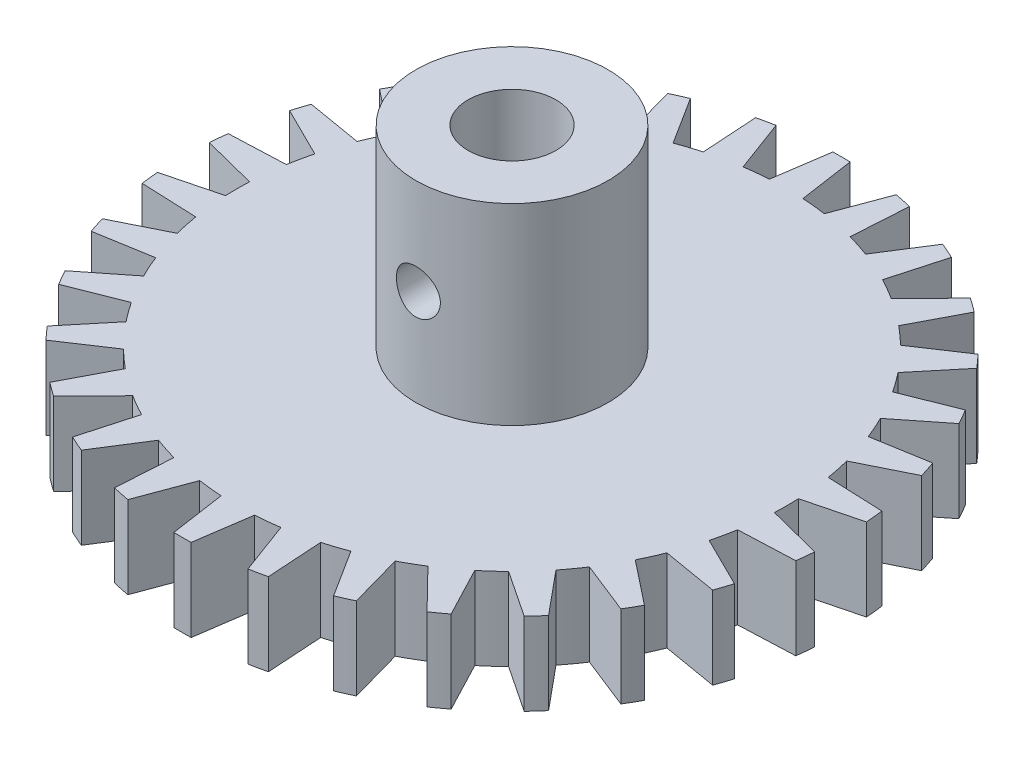
SolidWorks part; units mm, degrees
ref_plane "Front Plane" through (0, 0, 0) normal (0, 0, 1) x (1, 0, 0)
ref_plane "Top Plane" through (0, 0, 0) normal (0, 1, 0) x (1, 0, 0)
ref_plane "Right Plane" through (0, 0, 0) normal (1, 0, 0) x (0, 0, -1)
sketch "Sketch1" plane through (0, 0, 0) normal (0, 1, 0) x (1, 0, 0)
  line L0 (0, 0) -> (0, 12) construction
  line L1 (0, 0) -> (-0.3141, 11.9959) construction
  line L2 (0, 0) -> (-0.6105, 9.9813) construction
  line L3 (0, 0) -> (-1.0453, 9.9452) construction
  line L4 (-0.3141, 11.9959) -> (-0.6105, 9.9813)
  line L5 (0.3141, 11.9959) -> (0.6105, 9.9813)
  line L6 (2.1868, 11.7991) -> (1.4781, 9.8902)
  line L7 (2.8013, 11.6684) -> (2.6724, 9.6363)
  line L8 (4.5922, 11.0866) -> (3.5021, 9.3667)
  line L9 (5.1661, 10.831) -> (4.6175, 8.8701)
  line L10 (6.7969, 9.8895) -> (5.373, 8.4339)
  line L11 (7.3051, 9.5202) -> (6.3608, 7.7162)
  line L12 (8.7045, 8.2603) -> (7.0091, 7.1325)
  line L13 (9.1249, 7.7934) -> (7.8261, 6.2251)
  line L14 (10.2317, 6.27) -> (8.3389, 5.5194)
  line L15 (10.5458, 5.7259) -> (8.9493, 4.462)
  line L16 (11.3117, 4.0057) -> (9.3042, 3.665)
  line L17 (11.5058, 3.4082) -> (9.6815, 2.5038)
  line L18 (11.8973, 1.5663) -> (9.8629, 1.6505)
  line L19 (11.963, 0.9415) -> (9.9905, 0.4362)
  line L20 (11.963, -0.9415) -> (9.9905, -0.4362)
  line L21 (11.8973, -1.5663) -> (9.8629, -1.6505)
  line L22 (11.5058, -3.4082) -> (9.6815, -2.5038)
  line L23 (11.3117, -4.0057) -> (9.3042, -3.665)
  line L24 (10.5458, -5.7259) -> (8.9493, -4.462)
  line L25 (10.2317, -6.27) -> (8.3389, -5.5194)
  line L26 (9.1249, -7.7934) -> (7.8261, -6.2251)
  line L27 (8.7045, -8.2603) -> (7.0091, -7.1325)
  line L28 (7.3051, -9.5202) -> (6.3608, -7.7162)
  line L29 (6.7969, -9.8895) -> (5.373, -8.4339)
  line L30 (5.1661, -10.831) -> (4.6175, -8.8701)
  line L31 (4.5922, -11.0866) -> (3.5021, -9.3667)
  line L32 (2.8013, -11.6684) -> (2.6724, -9.6363)
  line L33 (2.1868, -11.7991) -> (1.4781, -9.8902)
  line L34 (0.3141, -11.9959) -> (0.6105, -9.9813)
  line L35 (-0.3141, -11.9959) -> (-0.6105, -9.9813)
  line L36 (-2.1868, -11.7991) -> (-1.4781, -9.8902)
  line L37 (-2.8013, -11.6684) -> (-2.6724, -9.6363)
  line L38 (-4.5922, -11.0866) -> (-3.5021, -9.3667)
  line L39 (-5.1661, -10.831) -> (-4.6175, -8.8701)
  line L40 (-6.7969, -9.8895) -> (-5.373, -8.4339)
  line L41 (-7.3051, -9.5202) -> (-6.3608, -7.7162)
  line L42 (-8.7045, -8.2603) -> (-7.0091, -7.1325)
  line L43 (-9.1249, -7.7934) -> (-7.8261, -6.2251)
  line L44 (-10.2317, -6.27) -> (-8.3389, -5.5194)
  line L45 (-10.5458, -5.7259) -> (-8.9493, -4.462)
  line L46 (-11.3117, -4.0057) -> (-9.3042, -3.665)
  line L47 (-11.5058, -3.4082) -> (-9.6815, -2.5038)
  line L48 (-11.8973, -1.5663) -> (-9.8629, -1.6505)
  line L49 (-11.963, -0.9415) -> (-9.9905, -0.4362)
  line L50 (-11.963, 0.9415) -> (-9.9905, 0.4362)
  line L51 (-11.8973, 1.5663) -> (-9.8629, 1.6505)
  line L52 (-11.5058, 3.4082) -> (-9.6815, 2.5038)
  line L53 (-11.3117, 4.0057) -> (-9.3042, 3.665)
  line L54 (-10.5458, 5.7259) -> (-8.9493, 4.462)
  line L55 (-10.2317, 6.27) -> (-8.3389, 5.5194)
  line L56 (-9.1249, 7.7934) -> (-7.8261, 6.2251)
  line L57 (-8.7045, 8.2603) -> (-7.0091, 7.1325)
  line L58 (-7.3051, 9.5202) -> (-6.3608, 7.7162)
  line L59 (-6.7969, 9.8895) -> (-5.373, 8.4339)
  line L60 (-5.1661, 10.831) -> (-4.6175, 8.8701)
  line L61 (-4.5922, 11.0866) -> (-3.5021, 9.3667)
  line L62 (-2.8013, 11.6684) -> (-2.6724, 9.6363)
  line L63 (-2.1868, 11.7991) -> (-1.4781, 9.8902)
  arc A0 (0.3141, 11.9959) -> (-0.3141, 11.9959) centre (0, 0) ccw
  arc A1 (-0.6105, 9.9813) -> (-1.0453, 9.9452) centre (0, 0) ccw
  arc A2 (0.6105, 9.9813) -> (1.0453, 9.9452) centre (0, 0) cw
  arc A4 (2.8013, 11.6684) -> (2.1868, 11.7991) centre (0, 0) ccw
  arc A5 (1.4781, 9.8902) -> (1.0453, 9.9452) centre (0, 0) ccw
  arc A6 (2.6724, 9.6363) -> (3.0902, 9.5106) centre (0, 0) cw
  arc A7 (5.1661, 10.831) -> (4.5922, 11.0866) centre (0, 0) ccw
  arc A8 (3.5021, 9.3667) -> (3.0902, 9.5106) centre (0, 0) ccw
  arc A9 (4.6175, 8.8701) -> (5, 8.6603) centre (0, 0) cw
  arc A10 (7.3051, 9.5202) -> (6.7969, 9.8895) centre (0, 0) ccw
  arc A11 (5.373, 8.4339) -> (5, 8.6603) centre (0, 0) ccw
  arc A12 (6.3608, 7.7162) -> (6.6913, 7.4314) centre (0, 0) cw
  arc A13 (9.1249, 7.7934) -> (8.7045, 8.2603) centre (0, 0) ccw
  arc A14 (7.0091, 7.1325) -> (6.6913, 7.4314) centre (0, 0) ccw
  arc A15 (7.8261, 6.2251) -> (8.0902, 5.8779) centre (0, 0) cw
  arc A16 (10.5458, 5.7259) -> (10.2317, 6.27) centre (0, 0) ccw
  arc A17 (8.3389, 5.5194) -> (8.0902, 5.8779) centre (0, 0) ccw
  arc A18 (8.9493, 4.462) -> (9.1355, 4.0674) centre (0, 0) cw
  arc A19 (11.5058, 3.4082) -> (11.3117, 4.0057) centre (0, 0) ccw
  arc A20 (9.3042, 3.665) -> (9.1355, 4.0674) centre (0, 0) ccw
  arc A21 (9.6815, 2.5038) -> (9.7815, 2.0791) centre (0, 0) cw
  arc A22 (11.963, 0.9415) -> (11.8973, 1.5663) centre (0, 0) ccw
  arc A23 (9.8629, 1.6505) -> (9.7815, 2.0791) centre (0, 0) ccw
  arc A24 (9.9905, 0.4362) -> (10, 0) centre (0, 0) cw
  arc A25 (11.8973, -1.5663) -> (11.963, -0.9415) centre (0, 0) ccw
  arc A26 (9.9905, -0.4362) -> (10, 0) centre (0, 0) ccw
  arc A27 (9.8629, -1.6505) -> (9.7815, -2.0791) centre (0, 0) cw
  arc A28 (11.3117, -4.0057) -> (11.5058, -3.4082) centre (0, 0) ccw
  arc A29 (9.6815, -2.5038) -> (9.7815, -2.0791) centre (0, 0) ccw
  arc A30 (9.3042, -3.665) -> (9.1355, -4.0674) centre (0, 0) cw
  arc A31 (10.2317, -6.27) -> (10.5458, -5.7259) centre (0, 0) ccw
  arc A32 (8.9493, -4.462) -> (9.1355, -4.0674) centre (0, 0) ccw
  arc A33 (8.3389, -5.5194) -> (8.0902, -5.8779) centre (0, 0) cw
  arc A34 (8.7045, -8.2603) -> (9.1249, -7.7934) centre (0, 0) ccw
  arc A35 (7.8261, -6.2251) -> (8.0902, -5.8779) centre (0, 0) ccw
  arc A36 (7.0091, -7.1325) -> (6.6913, -7.4314) centre (0, 0) cw
  arc A37 (6.7969, -9.8895) -> (7.3051, -9.5202) centre (0, 0) ccw
  arc A38 (6.3608, -7.7162) -> (6.6913, -7.4314) centre (0, 0) ccw
  arc A39 (5.373, -8.4339) -> (5, -8.6603) centre (0, 0) cw
  arc A40 (4.5922, -11.0866) -> (5.1661, -10.831) centre (0, 0) ccw
  arc A41 (4.6175, -8.8701) -> (5, -8.6603) centre (0, 0) ccw
  arc A42 (3.5021, -9.3667) -> (3.0902, -9.5106) centre (0, 0) cw
  arc A43 (2.1868, -11.7991) -> (2.8013, -11.6684) centre (0, 0) ccw
  arc A44 (2.6724, -9.6363) -> (3.0902, -9.5106) centre (0, 0) ccw
  arc A45 (1.4781, -9.8902) -> (1.0453, -9.9452) centre (0, 0) cw
  arc A46 (-0.3141, -11.9959) -> (0.3141, -11.9959) centre (0, 0) ccw
  arc A47 (0.6105, -9.9813) -> (1.0453, -9.9452) centre (0, 0) ccw
  arc A48 (-0.6105, -9.9813) -> (-1.0453, -9.9452) centre (0, 0) cw
  arc A49 (-2.8013, -11.6684) -> (-2.1868, -11.7991) centre (0, 0) ccw
  arc A50 (-1.4781, -9.8902) -> (-1.0453, -9.9452) centre (0, 0) ccw
  arc A51 (-2.6724, -9.6363) -> (-3.0902, -9.5106) centre (0, 0) cw
  arc A52 (-5.1661, -10.831) -> (-4.5922, -11.0866) centre (0, 0) ccw
  arc A53 (-3.5021, -9.3667) -> (-3.0902, -9.5106) centre (0, 0) ccw
  arc A54 (-4.6175, -8.8701) -> (-5, -8.6603) centre (0, 0) cw
  arc A55 (-7.3051, -9.5202) -> (-6.7969, -9.8895) centre (0, 0) ccw
  arc A56 (-5.373, -8.4339) -> (-5, -8.6603) centre (0, 0) ccw
  arc A57 (-6.3608, -7.7162) -> (-6.6913, -7.4314) centre (0, 0) cw
  arc A58 (-9.1249, -7.7934) -> (-8.7045, -8.2603) centre (0, 0) ccw
  arc A59 (-7.0091, -7.1325) -> (-6.6913, -7.4314) centre (0, 0) ccw
  arc A60 (-7.8261, -6.2251) -> (-8.0902, -5.8779) centre (0, 0) cw
  arc A61 (-10.5458, -5.7259) -> (-10.2317, -6.27) centre (0, 0) ccw
  arc A62 (-8.3389, -5.5194) -> (-8.0902, -5.8779) centre (0, 0) ccw
  arc A63 (-8.9493, -4.462) -> (-9.1355, -4.0674) centre (0, 0) cw
  arc A64 (-11.5058, -3.4082) -> (-11.3117, -4.0057) centre (0, 0) ccw
  arc A65 (-9.3042, -3.665) -> (-9.1355, -4.0674) centre (0, 0) ccw
  arc A66 (-9.6815, -2.5038) -> (-9.7815, -2.0791) centre (0, 0) cw
  arc A67 (-11.963, -0.9415) -> (-11.8973, -1.5663) centre (0, 0) ccw
  arc A68 (-9.8629, -1.6505) -> (-9.7815, -2.0791) centre (0, 0) ccw
  arc A69 (-9.9905, -0.4362) -> (-10, 0) centre (0, 0) cw
  arc A70 (-11.8973, 1.5663) -> (-11.963, 0.9415) centre (0, 0) ccw
  arc A71 (-9.9905, 0.4362) -> (-10, 0) centre (0, 0) ccw
  arc A72 (-9.8629, 1.6505) -> (-9.7815, 2.0791) centre (0, 0) cw
  arc A73 (-11.3117, 4.0057) -> (-11.5058, 3.4082) centre (0, 0) ccw
  arc A74 (-9.6815, 2.5038) -> (-9.7815, 2.0791) centre (0, 0) ccw
  arc A75 (-9.3042, 3.665) -> (-9.1355, 4.0674) centre (0, 0) cw
  arc A76 (-10.2317, 6.27) -> (-10.5458, 5.7259) centre (0, 0) ccw
  arc A77 (-8.9493, 4.462) -> (-9.1355, 4.0674) centre (0, 0) ccw
  arc A78 (-8.3389, 5.5194) -> (-8.0902, 5.8779) centre (0, 0) cw
  arc A79 (-8.7045, 8.2603) -> (-9.1249, 7.7934) centre (0, 0) ccw
  arc A80 (-7.8261, 6.2251) -> (-8.0902, 5.8779) centre (0, 0) ccw
  arc A81 (-7.0091, 7.1325) -> (-6.6913, 7.4314) centre (0, 0) cw
  arc A82 (-6.7969, 9.8895) -> (-7.3051, 9.5202) centre (0, 0) ccw
  arc A83 (-6.3608, 7.7162) -> (-6.6913, 7.4314) centre (0, 0) ccw
  arc A84 (-5.373, 8.4339) -> (-5, 8.6603) centre (0, 0) cw
  arc A85 (-4.5922, 11.0866) -> (-5.1661, 10.831) centre (0, 0) ccw
  arc A86 (-4.6175, 8.8701) -> (-5, 8.6603) centre (0, 0) ccw
  arc A87 (-3.5021, 9.3667) -> (-3.0902, 9.5106) centre (0, 0) cw
  arc A88 (-2.1868, 11.7991) -> (-2.8013, 11.6684) centre (0, 0) ccw
  arc A89 (-2.6724, 9.6363) -> (-3.0902, 9.5106) centre (0, 0) ccw
  arc A90 (-1.4781, 9.8902) -> (-1.0453, 9.9452) centre (0, 0) cw
  point P185 (0, 0)
  dimension "D1" = 1.5
  dimension "D2" = 2
  dimension "D3" = 2.5
  dimension "D4" = 30
  dimension "D5" = 10
extrude "Boss-Extrude1" add sketch "Sketch1" along normal blind 3
sketch "Sketch3" plane through (0, 3, 0) normal (0, 1, 0) x (1, 0, 0)
  circle A1 centre (0, 0) radius 3.5
  dimension "D2" = 7
extrude "Boss-Extrude2" add sketch "Sketch3" along normal blind 7
sketch "Sketch2" plane through (0, 3, 0) normal (0, 1, 0) x (1, 0, 0)
  circle A0 centre (0, 0) radius 1.6
  dimension "D1" = 3.2
extrude "Cut-Extrude1" cut sketch "Sketch2" against normal through all and the other way through all
sketch "Sketch4" plane through (0, 0, 0) normal (0, 0, 1) x (1, 0, 0)
  line L1 (3.5, 10) -> (-3.5, 10) construction
  circle A0 centre (0, 6.5) radius 0.8
  dimension "D1" = 1.6
  dimension "D2" = 3.5
extrude "Cut-Extrude2" cut sketch "Sketch4" along normal through all
